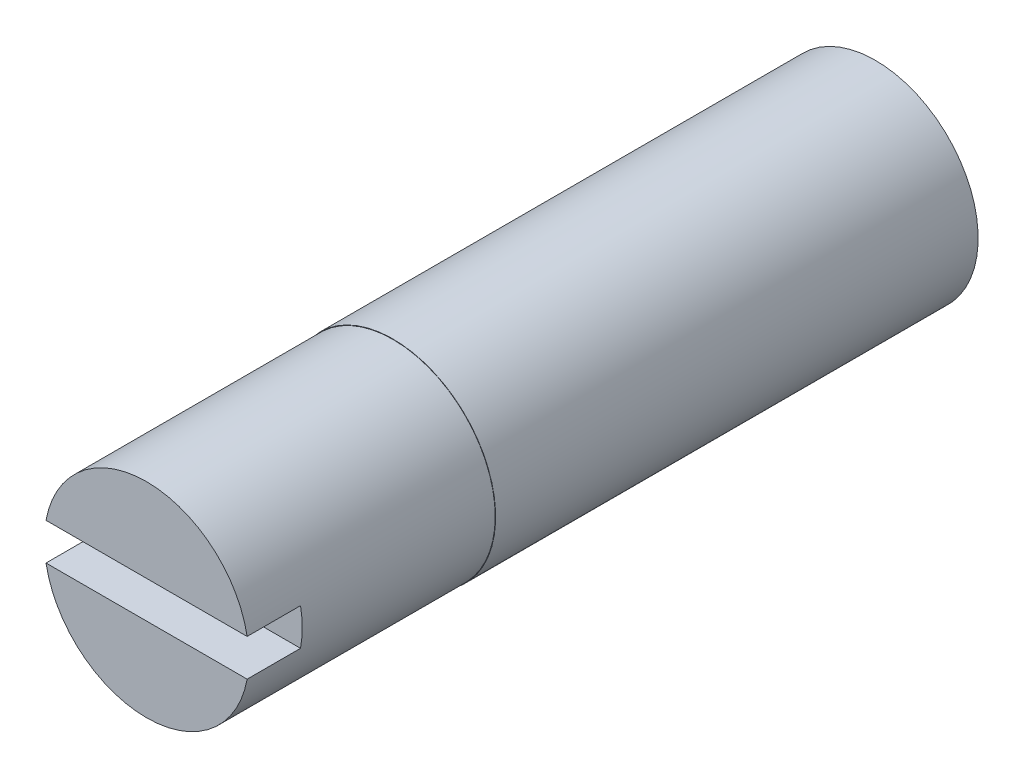
SolidWorks part; units mm, degrees
other "標示1"
sketch "草圖10" plane through (-2.5, -2.5, 3) normal (-0.9436, -0.3126, 0.109) x (0.3106, -0.9499, -0.0352)
ref_plane "前基準面" through (0, 0, 0) normal (0, 0, 1) x (1, 0, 0)
ref_plane "上基準面" through (0, 0, 0) normal (0, 1, 0) x (1, 0, 0)
ref_plane "右基準面" through (0, 0, 0) normal (1, 0, 0) x (0, 0, -1)
sketch "草圖1" plane through (0, 0, 0) normal (0, 0, 1) x (1, 0, 0)
  circle A0 centre (0, 0) radius 2.49
  dimension "D1" = 4.98
extrude "填料-伸長1" add sketch "草圖1" along normal blind 6
sketch "草圖8" plane through (0, 0, 6) normal (0, 0, 1) x (1, 0, 0)
  line L0 (0, 0) -> (2.5, 0)
  line L1 (2.5, -0.45) -> (2.5, 0.45)
  line L6 (0, 2.49) -> (0, -2.49)
  line L7 (2.5, -0.45) -> (-2.5, -0.45)
  line L8 (2.5, 0.45) -> (-2.5, 0.45)
  line L9 (-2.5, -0.45) -> (-2.5, 0.45)
  circle A0 centre (0, 0) radius 2.49 construction
  point P12 (0, -0.45)
  point P14 (0, 0.45)
  dimension "D1" = 0.45
  dimension "D2" = 2.5
extrude "除料-伸長2" cut sketch "草圖8" against normal blind 1.3 contours L1 L8 L6 L0 | L7 L1 L0 L6 | L9 L7 L6 L8 region at (1.25, 0.225, 6) region at (-1.25, 0, 6) region at (1.25, -0.225, 6)
sketch "草圖9" plane through (0, 0, 0) normal (0, 0, -1) x (-1, 0, 0)
  circle A0 centre (0, 0) radius 2.5
  dimension "D1" = 5
extrude "填料-伸長2" add sketch "草圖9" along normal blind 11.75
